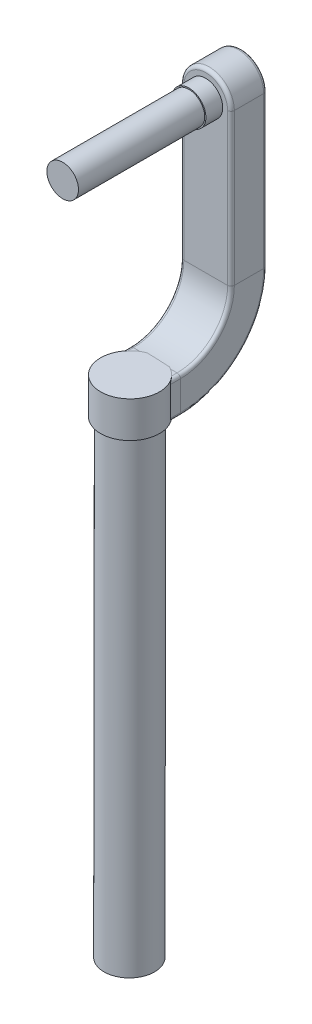
SolidWorks part; units mm, degrees
ref_plane "Front Plane" through (0, 0, 0) normal (0, 0, 1) x (1, 0, 0)
ref_plane "Top Plane" through (0, 0, 0) normal (0, 1, 0) x (1, 0, 0)
ref_plane "Right Plane" through (0, 0, 0) normal (1, 0, 0) x (0, 0, -1)
sketch "Sketch1" plane through (0, 0, 0) normal (0, 1, 0) x (1, 0, 0)
  line L0 (0, 0) -> (0, -76.2) construction
  line L1 (0, 0) -> (76.2, 0)
  line L2 (0, 0) -> (0, 54.4975)
  line L3 (0, 54.4975) -> (76.2, 54.4975)
  line L4 (76.2, 0) -> (76.2, 54.4975)
  line L5 (0, -76.2) -> (76.2, -76.2) construction
  line L6 (76.2, -76.2) -> (76.2, 0) construction
  dimension "D1" = 76.2
  dimension "D2" = 76.2
extrude "Boss-Extrude1" add sketch "Sketch1" along normal blind 228.6
fillet "Fillet1" radius 5.08 1 edges at (76.2, 114.3, 0)
fillet "Fillet2" radius 5.08 1 edges at (76.2, 114.3, -54.4975)
fillet "Fillet3" radius 5.08 1 edges at (0, 114.3, -54.4975)
fillet "Fillet4" radius 5.08 1 edges at (0, 114.3, 0)
sketch "Sketch4" plane through (0, 0, 0) normal (0, -1, 0) x (1, 0, 0)
sketch "Sketch9" plane through (0, 0, 0) normal (0, -1, 0) x (1, 0, 0)
revolve "Revolve1" add sketch "Sketch1<3>" angle 90 about L5 reverse direction yes
sketch "Sketch1<3>" plane through (0, 0, 0) normal (0, 1, 0) x (1, 0, 0) same geometry as "Sketch1"
fillet "Fillet5" radius 5.08 1 edges at (0, -53.8815, 22.3185)
fillet "Fillet6" radius 5.08 1 edges at (0, -92.4171, -16.2171)
fillet "Fillet7" radius 5.08 2 edges at (76.2, -92.4171, -16.2171) (76.2, -53.8815, 22.3185)
sketch "Sketch13" plane through (0, 0, 76.2) normal (0, 0, 1) x (1, 0, 0)
  line L0 (0, -130.6975) -> (0, -76.2)
  line L1 (76.2, -130.81) -> (0, -130.6975)
  line L2 (38.1, -130.7537) -> (38.1, -76.2)
  line L3 (0, -76.2) -> (76.2, -76.2)
  line L4 (76.2, -76.2) -> (76.2, -130.81)
  line L5 (67.818, -76.2) -> (76.2, -76.2)
  line L6 (71.12, -130.6975) -> (5.08, -130.6975) construction
  line L8 (76.2, -81.28) -> (76.2, -125.6175) construction
  line L11 (47.625, -130.7678) -> (47.625, -76.2)
  line L12 (76.2, -130.81) -> (67.818, -130.81)
  line L13 (76.2, -130.81) -> (76.2, -76.2)
  line L14 (76.2, -76.2) -> (67.818, -76.2)
  line L15 (67.818, -130.81) -> (67.818, -76.2)
  dimension "D1" = 76.2
  dimension "D2" = 54.61
  dimension "D3" = 9.525
  dimension "D4" = 8.382
sketch3d "3DSketch1" plane through (0, 0, 0) normal (0, 0, 1) x (1, 0, 0)
ref_plane "Plane1" through (76.2, 0, 0) normal (-1, 0, 0) x (0, -1, 0)
ref_plane "Plane5" through (-0.193, -130.6972, 0) normal (0.0015, 1, 0) x (-1, 0.0015, 0)
sketch "Sketch39" plane through (-0.193, -130.6972, 0) normal (0.0015, 1, 0) x (-1, 0.0015, 0)
  line L0 (-38.2931, 76.2) -> (-38.2931, 152.4) construction
  circle A0 centre (-38.2931, 114.3) radius 38.1
  circle A1 centre (-38.2931, 114.3) radius 44.45
  dimension "D1" = 76.2
ref_plane "Plane6" through (0, 0, 76.2) normal (0, 0, 1) x (1, 0, 0)
surface "Surface-Extrude1" sketch "Sketch39" parameters "D1"=17.78
extrude "Boss-Extrude6" add sketch "Sketch39" along normal blind 54.61 contours A1 | A0
sketch "Sketch50" plane through (-0.1124, -76.0872, 0) normal (0.0015, 1, 0) x (1, -0.0015, 0)
  line L0 (38.2931, -76.2) -> (38.2931, -152.4) construction
  circle A0 centre (38.2931, -114.3) radius 38.1 construction
  circle A1 centre (38.2931, -114.3) radius 38.1
extrude "Boss-Extrude7" add sketch "Sketch50" against normal blind 762
sketch "Sketch53" plane through (0, 228.6, 0) normal (0, 1, 0) x (1, 0, 0)
  line L0 (38.1, 54.4975) -> (38.1, 0)
  line L1 (71.12, 54.4975) -> (5.08, 54.4975) construction
  line L2 (5.08, 0) -> (71.12, 0) construction
sketch "Sketch54" plane through (0, 228.6, 0) normal (0, 1, 0) x (1, 0, 0)
  line L1 (38.1, 54.4975) -> (76.2, 54.4975)
  line L2 (38.1, 54.4975) -> (38.1, 0)
  line L3 (38.1, 0) -> (76.2, 0)
  line L4 (76.2, 54.4975) -> (76.2, 0)
  dimension "D1" = 54.4975
  dimension "D2" = 38.1
revolve "Revolve5" add sketch "Sketch54" angle 180 about L2
fillet "Fillet8" radius 5.08 1 edges at (38.1, 266.7, -54.4975)
fillet "Fillet9" radius 5.08 1 edges at (38.1, 266.7, 0)
sketch "Sketch56" plane through (0, 0, 0) normal (0, 0, 1) x (1, 0, 0)
  line L0 (71.12, 228.6) -> (5.08, 228.6) construction
  circle A0 centre (38.1, 228.6) radius 23.876
  dimension "D1" = 47.752
extrude "Boss-Extrude8" add sketch "Sketch56" along normal blind 215.9
sketch "Sketch59" plane through (0, 0, 0) normal (0, 0, 1) x (1, 0, 0)
  circle A0 centre (38.1, 228.6) radius 25.626
  dimension "D1" = 51.252
extrude "Boss-Extrude9" add sketch "Sketch59" along normal blind 25.4
sketch3d "3DSketch2"
  point P0 (24.8533, 206.6633, 15.2454)
